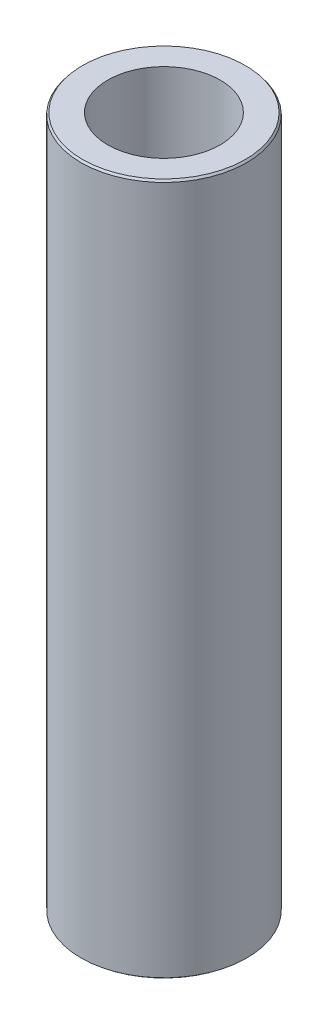
SolidWorks part; units mm, degrees
ref_plane "Front Plane" through (0, 0, 0) normal (0, 0, 1) x (1, 0, 0)
ref_plane "Top Plane" through (0, 0, 0) normal (0, 1, 0) x (1, 0, 0)
ref_plane "Right Plane" through (0, 0, 0) normal (1, 0, 0) x (0, 0, -1)
sketch "Sketch1" plane through (0, 0, 0) normal (0, 1, 0) x (1, 0, 0)
  circle A0 centre (0, 0) radius 30
  dimension "SHAFT_OD" = 60
extrude "Boss-Extrude1" add sketch "Sketch1" along normal blind 250.3188
sketch "Sketch2" plane through (0, 0, 0) normal (0, 1, 0) x (1, 0, 0)
  circle A0 centre (0, 0) radius 20.3253
  dimension "BORE_D" = 40.6506
extrude "Cut-Extrude1" cut sketch "Sketch2" along normal through all
chamfer "Chamfer1" distance 0.7034 angle 38.579 2 edges at (0, 250.3188, 30) (0, 0, 30) first distance on face at (0, 250.3188, 30) first distance on face at (0, 0, 20.3253)
